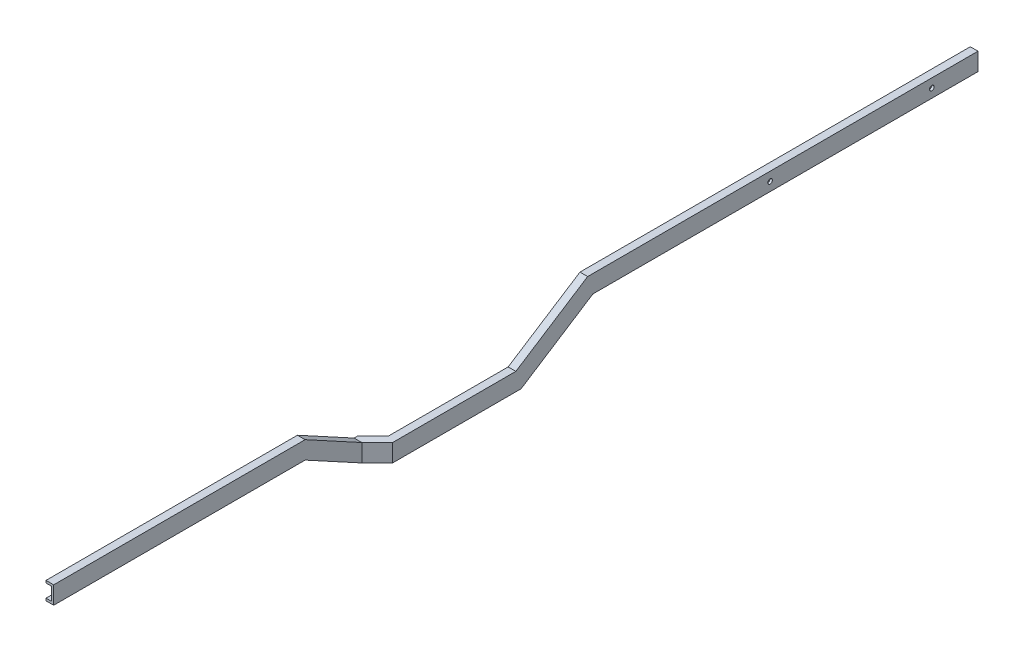
SolidWorks part; units mm, degrees
ref_plane "Front" through (0, 0, 0) normal (0, 0, 1) x (1, 0, 0)
ref_plane "Top" through (0, 0, 0) normal (0, 1, 0) x (1, 0, 0)
ref_plane "Right" through (0, 0, 0) normal (1, 0, 0) x (0, 0, -1)
sketch "草图1" plane through (0, 0, 0) normal (1, 0, 0) x (0, 0, -1)
  line L1 (295, -5.75) -> (-295, -5.75)
  line L2 (295, -5.75) -> (295, 5.75)
  line L3 (295, 5.75) -> (-295, 5.75)
  line L4 (-295, -5.75) -> (-295, 5.75)
  line L5 (295, -5.75) -> (-295, 5.75) construction
  line L6 (295, 5.75) -> (-295, -5.75) construction
  point P0 (0, 0)
  dimension "D1" = 590
  dimension "D2" = 11.5
extrude "凸台-拉伸1" add sketch "草图1" along normal blind 5
sketch "草图2" plane through (0, 0, 0) normal (-1, 0, 0) x (0, 0, 1)
  line L0 (295, 5.75) -> (295, -5.75) construction
  line L1 (295, -4.3811) -> (-295, -4.3811)
  line L2 (295, -4.3811) -> (295, 4.1189)
  line L3 (295, 4.1189) -> (-295, 4.1189)
  line L4 (-295, -4.3811) -> (-295, 4.1189)
  line L5 (295, -4.3811) -> (-295, 4.1189) construction
  line L6 (295, 4.1189) -> (-295, -4.3811) construction
  line L7 (-295, -5.75) -> (-295, 5.75) construction
  line L8 (-295, -0.1311) -> (295, -0.1311) construction
  point P0 (0, -0.1311)
  dimension "D1" = 8.5
extrude "切除-拉伸1" cut sketch "草图2" against normal blind 3.5
sketch "草图3" plane through (5, 0, 0) normal (1, 0, 0) x (0, 0, -1)
  line L0 (295, -5.75) -> (295, 5.75) construction
  line L1 (295, -5.75) -> (-95, -5.75)
  line L2 (295, -5.75) -> (295, 5.75)
  line L3 (295, 5.75) -> (-95, 5.75)
  line L4 (-95, -5.75) -> (-95, 5.75)
  line L5 (295, -5.75) -> (-95, 5.75) construction
  line L6 (295, 5.75) -> (-95, -5.75) construction
  line L7 (295, 5.75) -> (-295, 5.75) construction
  line L8 (-295, -5.75) -> (295, -5.75) construction
  point P0 (100, 0)
  dimension "D1" = 390
extrude "凸台-拉伸2" add sketch "草图3" along normal blind 10
chamfer "倒角1" distance 10 angle 45 1 edges at (15, 0, 95)
sketch "草图4" plane through (0, 5.75, 0) normal (0, 1, 0) x (1, 0, 0)
  line L0 (15, 295) -> (0, 295) construction
  line L2 (0, -92.9289) -> (0, 295)
  line L3 (0, 295) -> (10, 295)
  line L4 (10, -82.9289) -> (10, 295)
  line L5 (15, -85) -> (5, -95) construction
  line L6 (5, -95) -> (15, -85) construction
  line L7 (0, 295) -> (0, -295) construction
  line L8 (0, -92.9289) -> (10, -82.9289)
  line L9 (15, 295) -> (15, -85) construction
  dimension "D1" = 5
  dimension "D2" = 5
extrude "切除-拉伸2" cut sketch "草图4" against normal through all
sketch "草图5" plane through (10, 0, 0) normal (-1, 0, 0) x (0, 0, 1)
  line L0 (82.9289, -5.75) -> (82.9289, 5.75) construction
  line L1 (-295, 4.25) -> (82.9289, 4.25)
  line L2 (-295, 4.25) -> (-295, -4.25)
  line L3 (-295, -4.25) -> (82.9289, -4.25)
  line L4 (82.9289, 4.25) -> (82.9289, -4.25)
  line L5 (-295, 4.25) -> (82.9289, -4.25) construction
  line L6 (-295, -4.25) -> (82.9289, 4.25) construction
  line L7 (-295, -5.75) -> (-295, 5.75) construction
  line L8 (82.9289, 0) -> (-295, 0) construction
  point P0 (-106.0355, 0)
  dimension "D1" = 8.5
extrude "切除-拉伸3" cut sketch "草图5" against normal blind 3.5
sketch "草图7" plane through (46.4645, 0, 46.4645) normal (-0.7071, 0, -0.7071) x (-0.7071, 0, 0.7071)
  line L0 (65.7107, -5.75) -> (65.7107, -4.3811) construction
  line L1 (56.4479, 4.1189) -> (65.7107, 4.1189)
  line L2 (56.4479, 4.1189) -> (56.4479, -4.3811)
  line L3 (56.4479, -4.3811) -> (65.7107, -4.3811)
  line L4 (65.7107, 4.1189) -> (65.7107, -4.3811)
  line L5 (56.4479, 4.1189) -> (65.7107, -4.3811) construction
  line L6 (56.4479, -4.3811) -> (65.7107, 4.1189) construction
  line L8 (60.7609, -4.3811) -> (65.7107, -4.3811) construction
  line L9 (65.7107, 4.1189) -> (60.7609, 4.1189) construction
  point P0 (61.0793, -0.1311)
extrude "切除-拉伸5" cut sketch "草图7" against normal blind 2.5
sketch "草图8" plane through (0, 5.75, 0) normal (0, 1, 0) x (1, 0, 0)
  line L0 (5, -95) -> (5, -295) construction
  line L1 (5, -95) -> (0, -95)
  line L2 (5, -95) -> (5, -295)
  line L3 (5, -295) -> (0, -295)
  line L4 (0, -95) -> (0, -295)
  line L5 (5, -95) -> (0, -295) construction
  line L6 (5, -295) -> (0, -95) construction
  line L7 (0, -92.9289) -> (0, -295) construction
  line L8 (5, -295) -> (0, -295) construction
  point P0 (2.5, -195)
extrude "凸台-拉伸3" add sketch "草图8" along normal blind 20
sketch "草图9" plane through (5, 0, 0) normal (1, 0, 0) x (0, 0, -1)
  line L0 (-295, 14.25) -> (-131.7902, 14.25)
  line L1 (-295, 25.75) -> (-295, -5.75) construction
  line L2 (-131.7902, 14.25) -> (-95, -5.75)
  line L3 (-295, 14.25) -> (-295, -5.75)
  line L4 (-295, -5.75) -> (-95, -5.75)
  line L6 (-295, 25.75) -> (-95, 25.75) construction
  dimension "D1" = 11.5
extrude "切除-拉伸6" cut sketch "草图9" against normal through all
sketch "草图10" plane through (5, 0, 0) normal (1, 0, 0) x (0, 0, -1)
  line L0 (-95, 5.75) -> (-131.7902, 25.75)
  line L1 (-295, 25.75) -> (-95, 25.75) construction
  line L2 (-95, -5.75) -> (-131.7902, 14.25) construction
  line L3 (-131.7902, 25.75) -> (-95, 25.75)
  line L4 (-95, 25.75) -> (-95, 5.75)
extrude "切除-拉伸7" cut sketch "草图10" against normal through all
sketch "草图11" plane through (0, 0, 0) normal (-1, 0, 0) x (0, 0, 1)
  line L0 (295, 20) -> (121.2131, 20) construction
  line L1 (295, 25.75) -> (295, 14.25) construction
  line L2 (131.7902, 25.75) -> (95, 5.75) construction
  line L3 (132.1716, 24.25) -> (95.1401, 4.1189)
  line L4 (295, 15.75) -> (131.4089, 15.75)
  line L5 (295, 15.75) -> (295, 24.25)
  line L6 (295, 24.25) -> (132.1716, 24.25)
  line L8 (113.1539, 4.1189) -> (92.9289, 4.1189) construction
  line L9 (131.4089, 15.75) -> (110.0133, 4.1189)
  line L10 (113.1539, 4.1189) -> (131.7902, 14.25) construction
  line L11 (110.0133, 4.1189) -> (95.1401, 4.1189)
  dimension "D1" = 8.5
  dimension "D2" = 1.5
  dimension "D3" = 1.5
extrude "切除-拉伸8" cut sketch "草图11" against normal blind 3.5
sketch "草图12" plane through (0, 5.75, 0) normal (0, 1, 0) x (1, 0, 0)
  line L0 (15, 295) -> (10, 295) construction
  line L1 (10, 295) -> (15, 295)
  line L2 (10, 295) -> (10, -5)
  line L3 (10, -5) -> (15, -5)
  line L4 (15, 295) -> (15, -5)
  line L5 (10, 295) -> (15, -5) construction
  line L6 (10, -5) -> (15, 295) construction
  line L7 (15, 295) -> (15, -85) construction
  line L8 (10, -82.9289) -> (10, 295) construction
  point P0 (12.5, 145)
  dimension "D1" = 300
extrude "凸台-拉伸4" add sketch "草图12" along normal blind 30
sketch "草图13" plane through (15, 0, 0) normal (1, 0, 0) x (0, 0, -1)
  line L0 (-1.6196, -5.75) -> (45, 24.25)
  line L1 (-85, -5.75) -> (295, -5.75) construction
  line L2 (45, 24.25) -> (295, 24.25)
  line L3 (295, -5.75) -> (295, 35.75) construction
  line L4 (295, 24.25) -> (295, -5.75)
  line L5 (295, -5.75) -> (-1.6196, -5.75)
  line L6 (-5, 35.75) -> (295, 35.75) construction
  line L7 (-5, 35.75) -> (-5, 5.75) construction
  line L8 (-5, 5.75) -> (41.6196, 35.75)
  line L9 (41.6196, 35.75) -> (-5, 35.75)
  line L10 (-5, 35.75) -> (-5, 5.75)
  point P17 (18.3098, 20.75)
  dimension "D1" = 11.5
  dimension "D2" = 11.5
  dimension "D3" = 50
extrude "切除-拉伸9" cut sketch "草图13" against normal through all
sketch "草图15" plane through (10, 0, 0) normal (-1, 0, 0) x (0, 0, 1)
  line L0 (-295, 24.25) -> (-295, 35.75) construction
  line L1 (-44.5591, 25.75) -> (-295, 25.75)
  line L3 (-42.0605, 34.25) -> (-295, 34.25)
  line L4 (-295, 25.75) -> (-295, 34.25)
  line L5 (-42.0605, 34.25) -> (4.5591, 4.25)
  line L6 (82.9289, 4.25) -> (-13.9203, 4.25) construction
  line L7 (-295, 35.75) -> (-41.6196, 35.75) construction
  line L8 (-295, 24.25) -> (-45, 24.25) construction
  line L9 (5, 5.75) -> (-41.6196, 35.75) construction
  line L10 (-44.5591, 25.75) -> (-11.1484, 4.25)
  line L11 (-11.1484, 4.25) -> (4.5591, 4.25)
  line L12 (-45, 24.25) -> (-13.9203, 4.25) construction
  dimension "D1" = 1.5
  dimension "D2" = 1.5
  dimension "D3" = 1.5
  dimension "D4" = 1.5
extrude "切除-拉伸10" cut sketch "草图15" against normal blind 3.5
sketch "草图16" plane through (15, 0, 0) normal (1, 0, 0) x (0, 0, -1)
  line L0 (295, 30) -> (32.6841, 30) construction
  line L1 (295, 24.25) -> (295, 35.75) construction
  line L2 (-5, 5.75) -> (41.6196, 35.75) construction
  circle A0 centre (160, 30) radius 1.5
  circle A1 centre (265, 30) radius 1.5
  point P12 (139.9939, 28.5171)
  dimension "D1" = 3
  dimension "D2" = 3
  dimension "D3" = 30
  dimension "D4" = 105
extrude "切除-拉伸11" cut sketch "草图16" against normal through all
